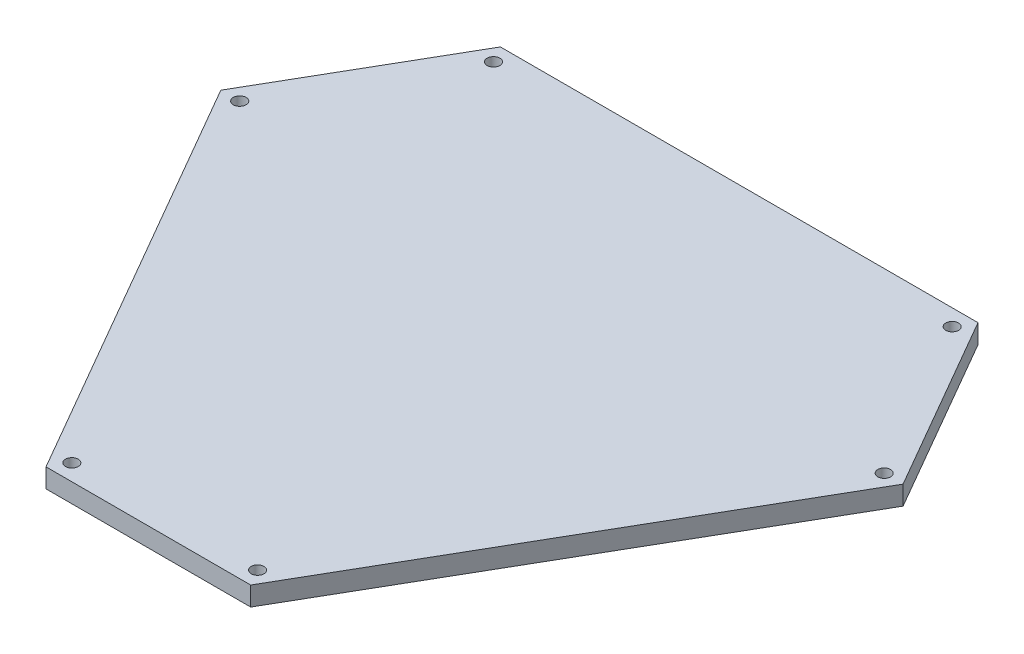
SolidWorks part; units mm, degrees
ref_plane "Front Plane" through (0, 0, 0) normal (0, 0, 1) x (1, 0, 0)
ref_plane "Top Plane" through (0, 0, 0) normal (0, 1, 0) x (1, 0, 0)
ref_plane "Right Plane" through (0, 0, 0) normal (1, 0, 0) x (0, 0, -1)
sketch "Sketch1" plane through (0, 0, 0) normal (0, 1, 0) x (1, 0, 0)
  line L0 (-106.25, 61.3435) -> (81.25, -46.9097) construction
  line L1 (87.5, 93.8194) -> (-87.5, 93.8194)
  line L2 (-87.5, 93.8194) -> (-125, 28.8675)
  line L3 (-125, 28.8675) -> (-37.5, -122.6869)
  line L4 (-37.5, -122.6869) -> (37.5, -122.6869)
  line L5 (37.5, -122.6869) -> (125, 28.8675)
  line L6 (125, 28.8675) -> (87.5, 93.8194)
  line L7 (106.25, 61.3435) -> (-81.25, -46.9097) construction
  line L8 (0, 93.8194) -> (0, -122.6869) construction
  line L9 (87.5, 93.8194) -> (-37.5, -122.6869) construction
  line L10 (-87.5, 93.8194) -> (37.5, -122.6869) construction
  line L11 (125, 28.8675) -> (-125, 28.8675) construction
  point P8 (0, 0)
  dimension "D1" = 175
  dimension "D2" = 75
  dimension "D3" = 120
extrude "Boss-Extrude1" add sketch "Sketch1" along normal blind 7
sketch "Sketch2" plane through (0, 7, 0) normal (0, 1, 0) x (1, 0, 0)
  circle A0 centre (118.0718, 28.8675) radius 2.35
  circle A1 centre (84.0359, 87.8194) radius 2.35
  circle A2 centre (-84.0359, 87.8194) radius 2.35
  circle A3 centre (-118.0718, 28.8675) radius 2.35
  circle A4 centre (-34.0359, -116.6869) radius 2.35
  circle A5 centre (34.0359, -116.6869) radius 2.35
  circle A6 centre (34.0359, -116.6869) radius 1.7 construction
  circle A9 centre (-34.0359, -116.6869) radius 1.7 construction
  circle A10 centre (-118.0718, 28.8675) radius 1.7 construction
  circle A11 centre (-84.0359, 87.8194) radius 1.7 construction
  circle A12 centre (118.0718, 28.8675) radius 1.7 construction
  circle A13 centre (84.0359, 87.8194) radius 1.7 construction
  dimension "D1" = 4.7
extrude "Cut-Extrude1" cut sketch "Sketch2" against normal blind 4
